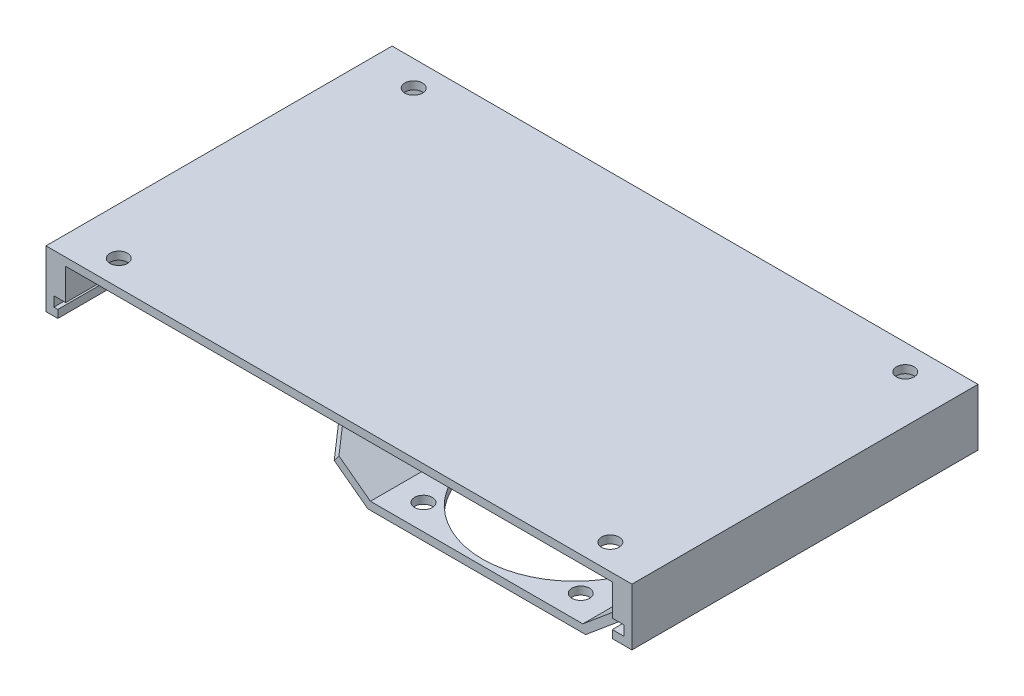
SolidWorks part; units mm, degrees
ref_plane "Front Plane" through (0, 0, 0) normal (0, 0, 1) x (1, 0, 0)
ref_plane "Top Plane" through (0, 0, 0) normal (0, 1, 0) x (1, 0, 0)
ref_plane "Right Plane" through (0, 0, 0) normal (1, 0, 0) x (0, 0, -1)
sketch "Sketch1" plane through (0, 0, 0) normal (0, 0, 1) x (1, 0, 0)
  line L0 (0, 0) -> (69.5, 0)
  line L1 (69.5, 0) -> (69.5, -8)
  line L2 (69.5, -8) -> (72.5, -8)
  line L3 (72.5, -8) -> (72.5, -10.5)
  line L4 (72.5, -10.5) -> (69.5, -10.5)
  line L5 (0, 0) -> (-69.5, 0)
  line L6 (-69.5, 0) -> (-69.5, -8)
  line L7 (-69.5, -8) -> (-72.5, -8)
  line L8 (-72.5, -8) -> (-72.5, -10.5)
  line L9 (-72.5, -10.5) -> (-71.5, -10.5)
  line L10 (74.5, -12.5) -> (69.5, -12.5)
  line L11 (74.5, -6) -> (74.5, -12.5)
  line L14 (0, 2) -> (71.5, 2)
  line L15 (0, 2) -> (-71.5, 2)
  line L18 (-74.5, -6) -> (-74.5, -12.5)
  line L19 (-74.5, -12.5) -> (-71.5, -12.5)
  line L20 (-71.5, -10.5) -> (-71.5, -12.5)
  line L21 (69.5, -10.5) -> (69.5, -12.5)
  line L22 (-74.5, -6) -> (-74.5, 2)
  line L23 (-74.5, 2) -> (-71.5, 2)
  line L24 (71.5, 2) -> (74.5, 2)
  line L25 (74.5, 2) -> (74.5, -6)
  line L27 (71.5, 2) -> (71.5, -6) construction
  line L28 (71.5, -6) -> (74.5, -6) construction
  line L29 (-71.5, 2) -> (-71.5, -6) construction
  line L30 (-71.5, -6) -> (-74.5, -6) construction
  dimension "D1" = 145
  dimension "D2" = 1
  dimension "D3" = 2.5
  dimension "D4" = 3
  dimension "D5" = 8
  dimension "D6" = 2
extrude "Boss-Extrude1" add sketch "Sketch1" along normal blind 85
sketch "Sketch2" plane through (0, 0, 0) normal (0, 0, -1) x (-1, 0, 0)
  line L0 (27, -48) -> (-27, -48)
  line L11 (74.5, -12.5) -> (27, -48)
  line L12 (-27, -48) -> (-69.5, -12.5)
  line L27 (-69.5, 0) -> (69.5, 0)
  line L28 (69.5, 0) -> (69.5, -8)
  line L29 (69.5, -8) -> (72.5, -8)
  line L30 (72.5, -8) -> (72.5, -10.5)
  line L31 (72.5, -10.5) -> (71.5, -10.5)
  line L32 (71.5, -10.5) -> (71.5, -12.5)
  line L33 (71.5, -12.5) -> (74.5, -12.5)
  line L34 (74.5, -12.5) -> (74.5, 2)
  line L35 (74.5, 2) -> (-74.5, 2)
  line L36 (-74.5, 2) -> (-74.5, -12.5)
  line L37 (-74.5, -12.5) -> (-69.5, -12.5)
  line L38 (-69.5, -12.5) -> (-69.5, -10.5)
  line L39 (-69.5, -10.5) -> (-72.5, -10.5)
  line L40 (-72.5, -10.5) -> (-72.5, -8)
  line L41 (-72.5, -8) -> (-69.5, -8)
  line L42 (-69.5, -8) -> (-69.5, 0)
  line L50 (74.5, -12.5) -> (74.5, 2)
  line L51 (74.5, 2) -> (-74.5, 2)
  line L52 (-74.5, 2) -> (-74.5, -12.5)
  line L53 (-74.5, -12.5) -> (-69.5, -12.5)
  point P3 (-25, -50)
  point P5 (25, -50)
  dimension "D5" = 0
extrude "Boss-Extrude2" add sketch "Sketch2" along normal blind 3
sketch "Sketch4" plane through (0, 0, -3) normal (0, 0, -1) x (-1, 0, 0)
  line L0 (43.0202, -36.027) -> (27, -48)
  line L1 (74.5, -12.5) -> (27, -48) construction
  line L2 (27, -48) -> (-27, -48)
  line L3 (-27, -48) -> (-42.3496, -35.1786)
  line L4 (-27, -48) -> (-69.5, -12.5) construction
  dimension "D1" = 20
extrude "Extrude-Thin1" add sketch "Sketch4" against normal blind 53 thin thin type one direction reverse wall 2
chamfer "Chamfer1" distance 10 angle 45 2 edges at (42.9907, -35.946, 50) (-43.6189, -36.828, 50)
chamfer "Chamfer2" distance 2 angle 45 2 edges at (-43.0202, -36.027, -1.5) (42.3496, -35.1786, -1.5)
sketch "Sketch5" plane through (0, 0, 0) normal (0, 0, 1) x (1, 0, 0)
  line L0 (-30, -31.267) -> (30, -31.267) construction
  line L1 (-30, -28.267) -> (30, -28.267)
  line L2 (-30, -34.267) -> (30, -34.267)
  line L3 (-69.5, 0) -> (69.5, 0) construction
  line L4 (0, 0) -> (0, -31.267) construction
  arc A0 (-30, -28.267) -> (-30, -34.267) centre (-30, -31.267) ccw
  arc A1 (30, -34.267) -> (30, -28.267) centre (30, -31.267) ccw
  point P2 (0, -31.267)
  dimension "D1" = 3
  dimension "D2" = 60
extrude "Cut-Extrude1" cut sketch "Sketch5" against normal blind 53
sketch "Sketch6" plane through (0, -48, 0) normal (0, 1, 0) x (1, 0, 0)
  line L0 (27, -50) -> (-27, 0) construction
  line L1 (-27, -50) -> (27, 0) construction
  line L2 (20, -43.5185) -> (-20, -43.5185) construction
  line L3 (-20, -43.5185) -> (-20, -6.4815) construction
  line L4 (-20, -6.4815) -> (20, -6.4815) construction
  line L5 (20, -6.4815) -> (20, -43.5185) construction
  line L6 (-27, 0) -> (27, 0) construction
  line L7 (27, -50) -> (27, 0) construction
  circle A0 centre (0, -25) radius 23.5
  circle A1 centre (20, -43.5185) radius 2.25
  circle A2 centre (-20, -43.5185) radius 2.25
  circle A3 centre (-20, -6.4815) radius 2.25
  circle A4 centre (20, -6.4815) radius 2.25
  dimension "D1" = 47
  dimension "D2" = 4.5
  dimension "D3" = 40
extrude "Cut-Extrude2" cut sketch "Sketch6" against normal blind 53
sketch "Sketch7" plane through (0, 2, 0) normal (0, 1, 0) x (1, 0, 0)
  line L0 (74.5, -78.5) -> (-74.5, -78.5) construction
  line L1 (74.5, -85) -> (74.5, 3) construction
  line L2 (-74.5, -85) -> (-74.5, 3) construction
  line L3 (74.5, -3.5) -> (-74.5, -3.5) construction
  line L4 (0, -78.5) -> (0, -59.4669) construction
  line L5 (0, -78.5) -> (0, -85) construction
  line L6 (74.5, -85) -> (-74.5, -85) construction
  line L7 (0, -3.5) -> (0, 3) construction
  line L8 (-74.5, 3) -> (74.5, 3) construction
  circle A0 centre (62.5, -78.5) radius 2.25
  circle A1 centre (62.5, -3.5) radius 2.25
  circle A2 centre (-62.5, -3.5) radius 2.25
  circle A3 centre (-62.5, -78.5) radius 2.25
  dimension "D2" = 62.5
  dimension "D4" = 4.5
  dimension "D1" = 75
  dimension "D3" = 62.5
extrude "Cut-Extrude3" cut sketch "Sketch7" against normal blind 53
